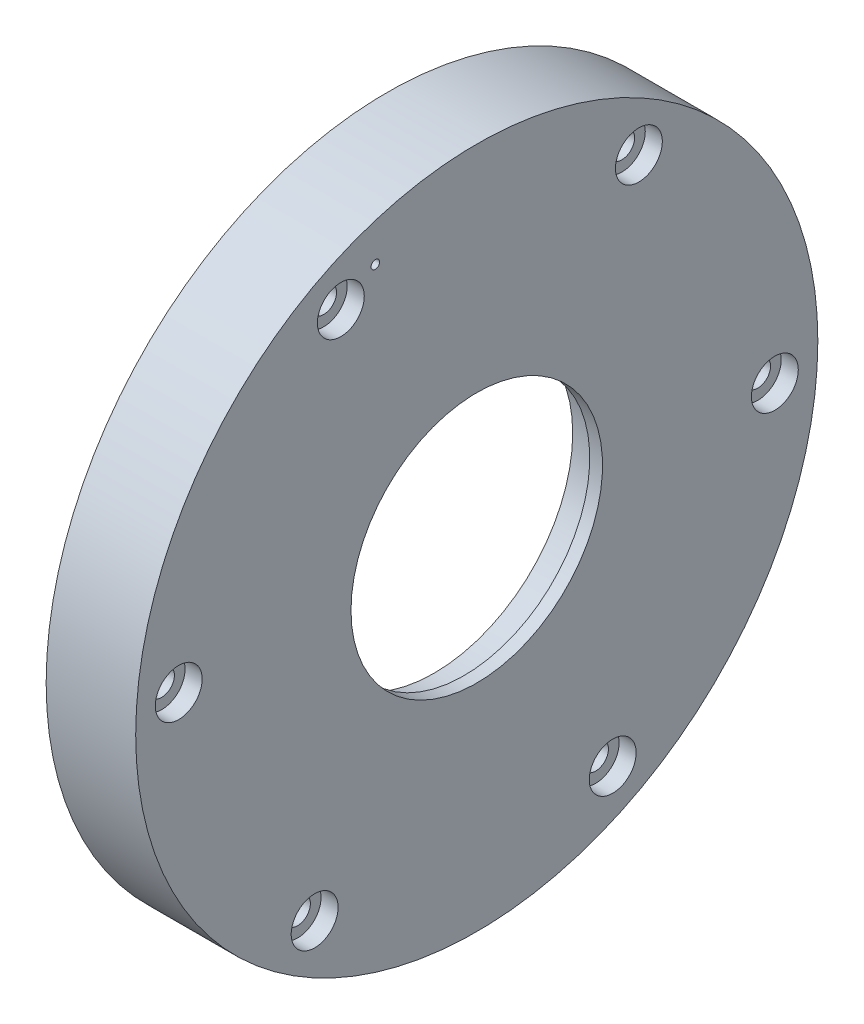
SolidWorks part; units mm, degrees
ref_plane "Front Plane" through (0, 0, 0) normal (0, 0, 1) x (1, 0, 0)
ref_plane "Top Plane" through (0, 0, 0) normal (0, 1, 0) x (1, 0, 0)
ref_plane "Right Plane" through (0, 0, 0) normal (1, 0, 0) x (0, 0, -1)
sketch "Sketch2" plane through (0, 0, 0) normal (0, 0, 1) x (1, 0, 0)
  line L0 (0, 0) -> (80.4799, 0) construction
  line L1 (0, 80) -> (0, 52.5)
  line L2 (0, 52.5) -> (11, 52.5)
  line L3 (11, 52.5) -> (11, 32.5)
  line L4 (11, 32.5) -> (18, 32.5)
  line L5 (18, 32.5) -> (18, 29.5)
  line L6 (18, 29.5) -> (21, 29.5)
  line L7 (21, 29.5) -> (21, 80)
  line L8 (21, 80) -> (0, 80)
  dimension "D1" = 80
  dimension "D2" = 32.5
  dimension "D3" = 52.5
  dimension "D4" = 18
  dimension "D5" = 3
  dimension "D6" = 7
  dimension "D7" = 3
revolve "Revolve1" add sketch "Sketch2" angle 360 about L0
sketch "Sketch3" plane through (0, 0, 0) normal (-1, 0, 0) x (0, 0, 1)
  circle A0 centre (0, 0) radius 60 construction
  circle A1 centre (0, 60) radius 2.5
  circle A2 centre (12.0779, 58.7718) radius 2.5
  circle A3 centre (23.6614, 55.1375) radius 2.5
  circle A4 centre (34.2761, 49.2458) radius 2.5
  circle A5 centre (43.4876, 41.338) radius 2.5
  circle A6 centre (50.9187, 31.7378) radius 2.5
  circle A7 centre (56.2651, 20.8383) radius 2.5
  circle A8 centre (59.3081, 9.0857) radius 2.5
  circle A9 centre (59.923, -3.039) radius 2.5
  circle A10 centre (58.0846, -15.0392) radius 2.5
  circle A11 centre (53.8683, -26.4236) radius 2.5
  circle A12 centre (47.4465, -36.7264) radius 2.5
  circle A13 centre (39.0823, -45.5255) radius 2.5
  circle A14 centre (29.1181, -52.4608) radius 2.5
  circle A15 centre (17.9618, -57.2484) radius 2.5
  circle A16 centre (6.0701, -59.6922) radius 2.5
  circle A17 centre (-6.0701, -59.6922) radius 2.5
  circle A18 centre (-17.9618, -57.2484) radius 2.5
  circle A19 centre (-29.1181, -52.4608) radius 2.5
  circle A20 centre (-39.0823, -45.5255) radius 2.5
  circle A21 centre (-47.4465, -36.7264) radius 2.5
  circle A22 centre (-53.8683, -26.4236) radius 2.5
  circle A23 centre (-58.0846, -15.0392) radius 2.5
  circle A24 centre (-59.923, -3.039) radius 2.5
  circle A25 centre (-59.3081, 9.0857) radius 2.5
  circle A26 centre (-56.2651, 20.8383) radius 2.5
  circle A27 centre (-50.9187, 31.7378) radius 2.5
  circle A28 centre (-43.4876, 41.338) radius 2.5
  circle A29 centre (-34.2761, 49.2458) radius 2.5
  circle A30 centre (-23.6614, 55.1375) radius 2.5
  circle A31 centre (-12.0779, 58.7718) radius 2.5
  point P67 (0, 0)
  dimension "D1" = 120
  dimension "D2" = 5
  dimension "D3" = 31
extrude "Cut-Extrude1" cut sketch "Sketch3" against normal blind 4
sketch "Sketch4" plane through (21, 0, 0) normal (1, 0, 0) x (0, 0, -1)
  circle A0 centre (-38.0255, -58.7712) radius 5.5
  circle A1 centre (-69.9102, 3.5454) radius 5.5
  circle A2 centre (-31.8846, 62.3167) radius 5.5
  circle A3 centre (38.0255, 58.7712) radius 5.5
  circle A4 centre (69.9102, -3.5454) radius 5.5
  circle A5 centre (31.8846, -62.3167) radius 5.5
  point P16 (0, 0)
  dimension "D2" = 11
  dimension "D1" = 6
extrude "Cut-Extrude2" cut sketch "Sketch4" against normal blind 4
sketch "Sketch5" plane through (21, 0, 0) normal (1, 0, 0) x (0, 0, -1)
  circle A0 centre (-38.0255, -58.7712) radius 3
  circle A1 centre (-69.9102, 3.5454) radius 3
  circle A2 centre (-31.8846, 62.3167) radius 3
  circle A3 centre (38.0255, 58.7712) radius 3
  circle A4 centre (69.9102, -3.5454) radius 3
  circle A5 centre (31.8846, -62.3167) radius 3
  point P16 (0, 0)
  dimension "D2" = 6
  dimension "D1" = 6
extrude "Cut-Extrude3" cut sketch "Sketch5" against normal through all
sketch "Sketch6" [suppressed] plane through (0, 0, 0) normal (-1, 0, 0) x (0, 0, 1)
  circle A0 centre (53.8756, 44.6925) radius 3
  circle A1 centre (65.6426, -24.3114) radius 3
  circle A2 centre (11.7671, -69.0039) radius 3
  circle A3 centre (-53.8756, -44.6925) radius 3
  circle A4 centre (-65.6426, 24.3114) radius 3
  circle A5 centre (-11.7671, 69.0039) radius 3
  point P15 (0, 0)
  dimension "D2" = 6
  dimension "D1" = 6
extrude "Cut-Extrude4" [suppressed] cut sketch "Sketch6" against normal blind 11
sketch "Sketch7" [suppressed] plane through (21, 0, 0) normal (-1, 0, 0) x (0, 0, 1)
  circle A0 centre (53.8756, 44.6925) radius 3.3
  circle A1 centre (65.6426, -24.3114) radius 3.3
  circle A2 centre (11.7671, -69.0039) radius 3.3
  circle A3 centre (-53.8756, -44.6925) radius 3.3
  circle A4 centre (-65.6426, 24.3114) radius 3.3
  circle A5 centre (-11.7671, 69.0039) radius 3.3
  point P15 (0, 0)
  dimension "D1" = 6.6
  dimension "D2" = 6
extrude "Cut-Extrude5" [suppressed] cut sketch "Sketch7" against normal through all
sketch "Sketch8" plane through (21, 0, 0) normal (1, 0, 0) x (0, 0, -1)
  circle A0 centre (-23.7966, 67.4351) radius 1
  dimension "D1" = 2
extrude "Cut-Extrude6" cut sketch "Sketch8" against normal blind 2
sketch "Sketch9" [suppressed] plane through (0, 0, 0) normal (-1, 0, 0) x (0, 0, 1)
  circle A0 centre (2.5177, -71.4663) radius 1
  dimension "D1" = 2
extrude "Cut-Extrude7" [suppressed] cut sketch "Sketch9" against normal blind 2
sketch "Sketch10" [suppressed] plane through (21, 0, 0) normal (1, 0, 0) x (0, 0, -1)
  line L0 (11.7671, 69.0039) -> (-11.7671, -69.0039) construction
  line L1 (-15.2814, 41.2611) -> (0, 0) construction
  circle A0 centre (0, 0) radius 44 construction
  circle A1 centre (-15.2814, 41.2611) radius 3.3
  circle A2 centre (43.3739, -7.3964) radius 3.3
  circle A3 centre (-28.0924, -33.8647) radius 3.3
  point P15 (0, 0)
  dimension "D1" = 6.6
  dimension "D2" = 88
  dimension "D3" = 30
  dimension "D4" = 3
extrude "Cut-Extrude8" [suppressed] cut sketch "Sketch10" against normal up to next
chamfer "Chamfer1" [suppressed] distance 0.5 angle 45
equation "\"R_ROLL\"= 5mm"
equation "\"D_SUN\"= 120mm"
equation "\"NUM_ROLL\"= 31"
equation "\"RHO\"= 1mm"
equation "\"D_SHAFT\"= 28mm"
equation "\"D_OUTPUT\"= 80mm"
equation "\"NUM_OUT\"= 8"
equation "\"R_OUT_ROLL\"= 5mm"
equation "\"D1@Sketch3\"=\"D_SUN\""
